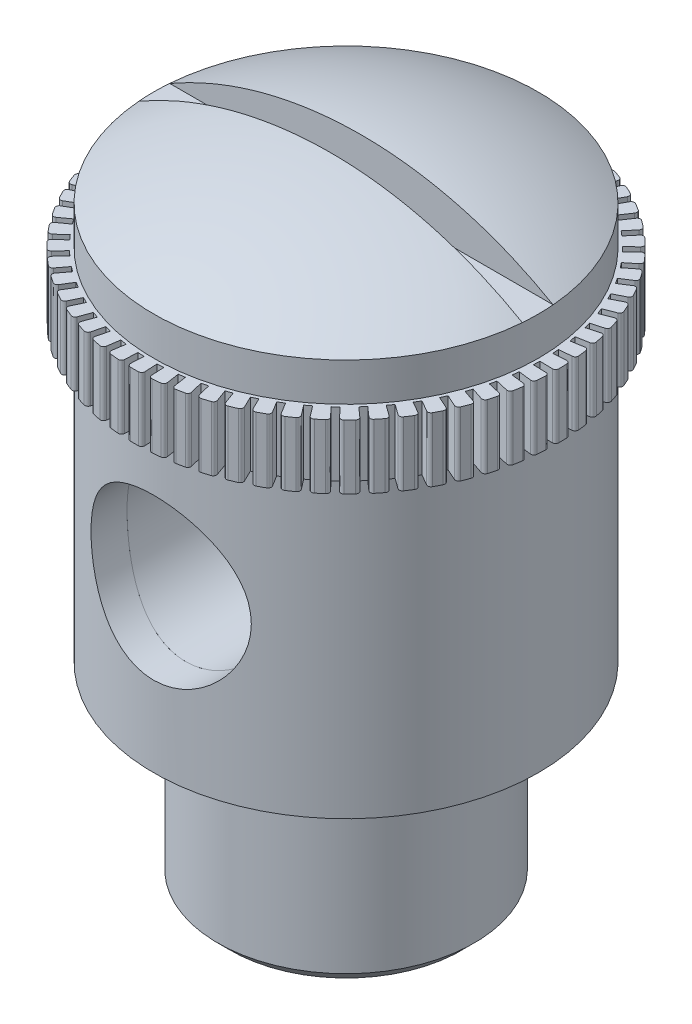
SolidWorks part; units mm, degrees
ref_plane "前视基准面" through (0, 0, 0) normal (0, 0, 1) x (1, 0, 0)
ref_plane "上视基准面" through (0, 0, 0) normal (0, 1, 0) x (1, 0, 0)
ref_plane "右视基准面" through (0, 0, 0) normal (1, 0, 0) x (0, 0, -1)
sketch "草图1" plane through (0, 0, 0) normal (0, 0, 1) x (1, 0, 0)
  line L0 (-6, 0) -> (6, 0) construction
  line L1 (0, 0) -> (0, -11) construction
  line L2 (0, -11) -> (-4, -11)
  line L3 (-4, -11) -> (-4, -5.9)
  line L4 (-4, -5.9) -> (-3.2, -5.9)
  line L5 (-3.2, -5.9) -> (-3.2, -5)
  line L6 (-3.2, -5) -> (-6, -5)
  line L7 (-6, -5) -> (-6, 7.3923)
  line L8 (-5, -5) -> (-5, 0) construction
  line L9 (0, 9) -> (6, 9) construction
  line L10 (6, 9) -> (6, 7.3923) construction
  line L11 (0, 9) -> (6, 7.3923) construction
  arc A0 (-6, 7.3923) -> (6, 7.3923) centre (0, -3) cw
  circle A1 centre (0, 0) radius 2.5
  point P14 (-1.5, -11)
  dimension "d1" = 5
  dimension "H" = 20
  dimension "l" = 6
  dimension "D" = 12
  dimension "(d)" = 8
  dimension "d2" = 3
  dimension "d3" = 10
  dimension "D4" = 10
  dimension "D5" = 5.1
  dimension "D6" = 6.4
  dimension "D7" = 15
sketch "草图2" plane through (0, 0, 0) normal (0, 0, 1) x (1, 0, 0)
  line L0 (-6, -5) -> (-6, 7.3923) construction
  line L1 (-3.2, -5) -> (-6, -5) construction
  line L2 (-3.2, -5.9) -> (-3.2, -5) construction
  line L3 (-4, -5.9) -> (-3.2, -5.9) construction
  line L4 (-4, -11) -> (-4, -5.9) construction
  line L5 (0, -11) -> (-4, -11) construction
  line L6 (0, 0) -> (0, -11) construction
  line L7 (-6, 6.1962) -> (-6, 7.3923)
  line L8 (-3.2, -5) -> (-5, -5)
  line L9 (-3.2, -5.9) -> (-3.2, -5)
  line L10 (-4, -5.9) -> (-3.2, -5.9)
  line L11 (-4, -10.6) -> (-4, -5.9)
  line L12 (-1.5, -11) -> (-3.6, -11)
  line L13 (0, 9) -> (0, 5)
  line L14 (-6, 6.1962) -> (-4, 6.1962)
  line L15 (-4, 6.1962) -> (-4, 5)
  line L16 (-4, 5) -> (-5, 5)
  line L17 (-5, 5) -> (-5, -5)
  line L18 (-5, -5) -> (-5, 0) construction
  line L19 (-5, -5) -> (-6, -5) construction
  line L20 (-4, -10.6) -> (-3.6, -11)
  line L21 (-1.5, -11) -> (-1.5, 4.134)
  line L22 (-1.5, 4.134) -> (0, 5)
  arc A0 (6, 7.3923) -> (-6, 7.3923) centre (0, -3) ccw construction
  arc A1 (0, 9) -> (-6, 7.3923) centre (0, -3) ccw
  dimension "D1" = 45
  dimension "D2" = 0.4
  dimension "D3" = 60
revolve "旋转1" add sketch "草图2" angle 360 about L13
cosmetic thread "装饰螺纹线1" parameters "D2"=6.8
sketch "草图3" plane through (0, 0, 0) normal (0, 0, 1) x (1, 0, 0)
  line L0 (-5, 6.1962) -> (-5, -5)
  line L1 (-6, 6.1962) -> (6, 6.1962) construction
  line L2 (-5, -5) -> (-6, -5)
  line L3 (-6, -5) -> (-6, 4.1962)
  line L4 (-6.6, 6.1962) -> (-5, 6.1962)
  line L5 (-6, 4.1962) -> (-6.6, 4.1962)
  line L6 (-6.6, 4.1962) -> (-6.6, 6.1962)
  line L7 (-6, -5) -> (-6, 7.3923) construction
  dimension "D1" = 0.6
  dimension "D2" = 2
revolve "旋转2" add sketch "草图3" angle 360 about L13
sketch "草图4" plane through (0, 0, 0) normal (0, 0, 1) x (1, 0, 0)
  circle A1 centre (0, 0) radius 2.5
  circle A2 centre (0, 0) radius 2.5 construction
extrude "切除-拉伸1" cut sketch "草图4" along normal through all
sketch "草图5" plane through (0, 0, 0) normal (0, 1, 0) x (1, 0, 0)
  line L0 (-0.1, 6.1) -> (0.1, 6.1)
  line L1 (-0.1, 6.6) -> (0.1, 6.6)
  line L2 (-0.1, 6.6) -> (-0.1, 6.1)
  line L4 (0.1, 6.6) -> (0.1, 6.1)
  circle A0 centre (0, 0) radius 6.6 construction
  circle A4 centre (0, 0) radius 6 construction
  point P4 (0, 6.6)
  dimension "D1" = 0.2
  dimension "D2" = 0.1
extrude "切除-拉伸3" cut sketch "草图5" along normal through all
fillet "圆角1" radius 0.1 2 edges at (0.1, 5.1962, -6.5992) (-0.1, 5.1962, -6.5992)
pattern_circular "阵列(圆周)1" count 63 over 360 of "切除-拉伸3", "圆角1"
sketch "草图6" plane through (0, 0, 0) normal (1, 0, 0) x (0, 0, -1)
  line L0 (-6, 7.3923) -> (6, 7.3923) construction
  line L1 (-0.48, 9) -> (0.48, 9)
  line L2 (-0.48, 9) -> (-0.48, 7.3923)
  line L3 (-0.48, 7.3923) -> (0.48, 7.3923)
  line L4 (0.48, 9) -> (0.48, 7.3923)
  arc A0 (6, 7.3923) -> (-6, 7.3923) centre (0, -3) ccw construction
  point P4 (0, 9)
  dimension "D1" = 0.96
extrude "切除-拉伸4" cut sketch "草图6" against normal through all and the other way through all
